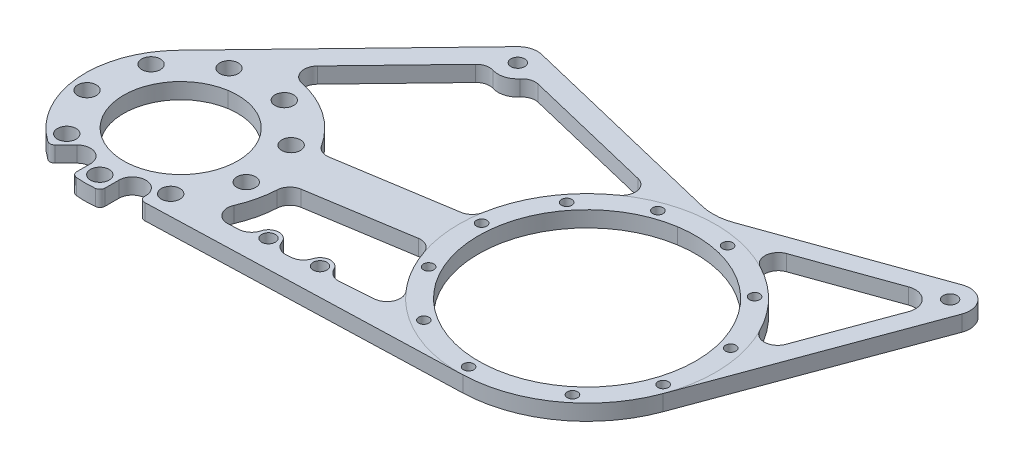
SolidWorks part; units mm, degrees
material "6061-T6 (SS)"
ref_plane "X-Y Datum" through (0, 0, 0) normal (0, 0, 1) x (1, 0, 0)
ref_plane "X-Z Datum" through (0, 0, 0) normal (0, 1, 0) x (1, 0, 0)
ref_plane "Y-Z Datum" through (0, 0, 0) normal (1, 0, 0) x (0, 0, -1)
sketch "Sketch3" plane through (0, 0, 0) normal (0, 1, 0) x (-1, 0, 0)
  line L0 (-549.8243, 18.1523) -> (-469.5602, 101.4499)
  line L1 (-673.8096, 168.3573) -> (-525.126, 173.1137)
  line L2 (-768.7537, 22.6435) -> (-729.9149, 127.9078)
  line L3 (-756.6081, 10.3783) -> (-668.3871, 41.9507)
  line L4 (-668.3871, 41.9507) -> (-558.9202, 15.5028)
  line L5 (-671.83, 106.4765) -> (-502.666, 133.35) construction
  line L8 (-479.4661, 170.6667) -> (-484.731, 165.4018)
  line L9 (-495.8272, 169.998) -> (-495.8272, 176.5707)
  line L10 (-509.5048, 176.5707) -> (-509.5048, 169.998)
  line L11 (-522.5048, 169.998) -> (-522.5048, 170.575)
  circle A1 centre (-759.8176, 19.3463) radius 9.525 construction
  circle A2 centre (-671.83, 106.4765) radius 61.9125 construction
  arc A4 (-671.83, 166.1265) -> (-671.83, 161.1265) centre (-671.83, 163.6265) ccw
  arc A5 (-671.83, 161.1265) -> (-671.83, 166.1265) centre (-671.83, 163.6265) ccw
  circle A8 centre (-556.6832, 24.7614) radius 9.525 construction
  circle A9 centre (-556.6832, 24.7614) radius 3.3
  arc A10 (-768.7537, 22.6435) -> (-756.6081, 10.3783) centre (-759.8176, 19.3463) ccw
  arc A11 (-558.9202, 15.5028) -> (-549.8243, 18.1523) centre (-556.6832, 24.7614) ccw
  arc A12 (-729.9149, 127.9078) -> (-673.8096, 168.3573) centre (-671.83, 106.4765) cw
  arc A13 (-525.126, 173.1137) -> (-522.5048, 170.575) centre (-525.0448, 170.575) cw
  arc A14 (-476.2083, 170.9479) -> (-469.5602, 101.4499) centre (-502.666, 133.35) cw
  arc A16 (-526.3535, 172.7519) -> (-476.2083, 170.9479) centre (-502.666, 133.35) ccw construction
  arc A17 (-476.2083, 170.9479) -> (-479.4661, 170.6667) centre (-477.6701, 168.8707) ccw
  arc A18 (-495.8272, 169.998) -> (-484.731, 165.4018) centre (-489.3272, 169.998) ccw
  arc A19 (-495.8272, 176.5707) -> (-498.1158, 179.0983) centre (-498.3672, 176.5707) ccw
  arc A20 (-498.1158, 179.0983) -> (-507.2162, 179.0983) centre (-502.666, 133.35) ccw
  arc A21 (-507.2162, 179.0983) -> (-509.5048, 176.5707) centre (-506.9648, 176.5707) ccw
  arc A22 (-522.5048, 169.998) -> (-509.5048, 169.998) centre (-516.0048, 169.998) ccw
  arc A23 (-522.5048, 170.575) -> (-526.3535, 172.7519) centre (-525.0448, 170.575) ccw construction
  arc A24 (-761.9822, 21.8372) -> (-757.653, 16.8554) centre (-759.8176, 19.3463) ccw
  arc A25 (-757.653, 16.8554) -> (-761.9822, 21.8372) centre (-759.8176, 19.3463) ccw
  arc A27 (-752.0152, 13.883) -> (-766.0654, 26.536) centre (-759.8176, 19.3463) ccw construction
  arc A29 (-548.0506, 28.7869) -> (-566.0335, 22.9455) centre (-556.6832, 24.7614) ccw construction
  arc A31 (-553.4437, 25.3906) -> (-559.9227, 24.1323) centre (-556.6832, 24.7614) ccw
  circle A33 centre (-502.666, 172.35) radius 4.5
  circle A36 centre (-502.666, 133.35) radius 27.4955
  circle A37 centre (-671.83, 106.4765) radius 52.3875
  dimension "D1" = 54.991
  dimension "D2" = 9
  dimension "D3" = 104.775
  dimension "D4" = 123.825
  dimension "D5" = 2.5
  dimension "D6" = 45.974
  dimension "D7" = 2.54
  dimension "D8" = 6.5
  dimension "D9" = 3.3
  dimension "D10" = 9.525
  dimension "D11" = 476.2083
  dimension "D12" = 477.6701
  dimension "D13" = 479.4661
  dimension "D14" = 484.731
  dimension "D15" = 13.883
  dimension "D16" = 22.9455
  dimension "D17" = 133.35
  dimension "D25" = 548.0506
  dimension "D26" = 553.4437
  dimension "D27" = 556.6832
  dimension "D28" = 559.9227
  dimension "D29" = 566.0335
  dimension "D30" = 671.83
  dimension "D31" = 752.0152
  dimension "D32" = 757.653
  dimension "D33" = 759.8176
  dimension "D34" = 761.9822
  dimension "D35" = 766.0654
  dimension "D36" = 106.4765
  dimension "D38" = 163.6265
  dimension "D45" = 172.35
extrude "Boss-Extrude2" add sketch "Sketch3" along normal blind 7.62 contours A22 L11 A13 L1 A12 L2 A10 L3 L4 A11 L0 A14 A17 L8 A18 L9 A19 A20 A21 L10 A37 A36 A33 A25 A24 A9 A5 A4 region at (600.4617, 0, 92.9965)
pattern_circular "CirPattern3" count 11 every 32 about axis through (671.83, 7.62, 106.4765) along (0, -1, 0) of face at (671.83, 7.62, 166.1265)
ref_point "Point1"
ref_point "Point2"
ref_plane "Plane1" through (671.83, 0, 106.4765) normal (-0.9876, 0, 0.1569) x (0.1569, 0, 0.9876)
ref_plane "Plane2" through (502.666, 0, 133.35) normal (-0.9876, 0, 0.1569) x (0.1569, 0, 0.9876)
split line "Split Line1"
split line "Split Line2"
sketch "Sketch4" plane through (0, 7.62, 0) normal (0, 1, 0) x (1, 0, 0)
  arc A0 (673.8096, -168.3573) -> (729.9149, -127.9078) centre (671.83, -106.4765) ccw construction
  arc A1 (673.8096, -168.3573) -> (729.9149, -127.9078) centre (671.83, -106.4765) ccw
  circle A2 centre (671.83, -106.4765) radius 61.9125
split line "Split Line3"
pattern_circular "CirPattern4" count 9 over 360 about axis through (502.666, 7.62, 133.35) along (0, -1, 0) of face at (502.666, 7.62, 176.85)
sketch "Sketch5" plane through (0, 7.62, 0) normal (0, 1, 0) x (1, 0, 0)
  line L0 (759.8176, -19.3463) -> (715.8226, -62.9126) construction
  line L1 (754.8899, -34.5364) -> (732.6394, -94.8414)
  line L2 (744.58, -24.1251) -> (684.06, -45.7839)
  line L3 (673.8096, -168.3573) -> (525.126, -173.1137) construction
  line L4 (756.6081, -10.3783) -> (668.3871, -41.9507) construction
  line L5 (756.6081, -10.3783) -> (668.3871, -41.9507) construction
  line L6 (768.7537, -22.6435) -> (729.9149, -127.9078) construction
  line L7 (768.7537, -22.6435) -> (729.9149, -127.9078) construction
  line L15 (556.6832, -24.7614) -> (556.6832, 0)
  line L16 (556.6832, 0) -> (624.6859, 0)
  line L17 (569.8883, 0) -> (569.8883, -158.2149) construction
  line L18 (593.9802, 0) -> (593.9802, -157.4442) construction
  line L19 (673.8096, -168.3573) -> (525.126, -173.1137) construction
  line L22 (593.9802, -157.4442) -> (569.8883, -158.2149) construction
  circle A0 centre (556.6832, -24.7614) radius 9.525 construction
  circle A1 centre (556.6832, -24.7614) radius 3.3 construction
  arc A2 (757.653, -16.8554) -> (761.9822, -21.8372) centre (759.8176, -19.3463) ccw construction
  arc A3 (761.9822, -21.8372) -> (757.653, -16.8554) centre (759.8176, -19.3463) ccw construction
  circle A4 centre (556.6832, -24.7614) radius 9.525 construction
  circle A5 centre (556.6832, -24.7614) radius 3.3 construction
  arc A6 (757.653, -16.8554) -> (761.9822, -21.8372) centre (759.8176, -19.3463) ccw construction
  arc A7 (761.9822, -21.8372) -> (757.653, -16.8554) centre (759.8176, -19.3463) ccw construction
  circle A8 centre (759.8176, -19.3463) radius 9.525 construction
  circle A9 centre (759.8176, -19.3463) radius 9.525 construction
  circle A10 centre (747.3044, -31.7376) radius 8.0853 construction
  circle A11 centre (569.8883, -158.2149) radius 3.3
  arc A13 (729.9149, -127.9078) -> (673.8096, -168.3573) centre (671.83, -106.4765) ccw construction
  arc A15 (754.8899, -34.5364) -> (744.58, -24.1251) centre (747.3044, -31.7376) ccw
  circle A31 centre (593.9802, -157.4442) radius 3.3
  circle A32 centre (593.9802, -157.4442) radius 5.08 construction
  circle A33 centre (569.8883, -158.2149) radius 5.08 construction
  arc A34 (732.6394, -94.8414) -> (684.06, -45.7839) centre (671.83, -106.4765) ccw
  dimension "D14" = 6.6
  dimension "D16" = 10.16
  dimension "D1" = 8.89
  dimension "D2" = 8.89
  dimension "D5" = 24.7614
  dimension "D7" = 13.2051
  dimension "D9" = 10.16
  dimension "D11" = 24.092
extrude "Cut-Extrude1" cut sketch "Sketch5" against normal blind 7.62 contours A34 L1 A15 L2 | A31 | A11 region at (728.4769, 7.62, 50.3816) region at (569.8883, 7.62, 158.2149) region at (593.9802, 7.62, 157.4442)
sketch "Sketch7" plane through (0, 7.62, 0) normal (0, 1, 0) x (1, 0, 0)
  line L0 (611.6874, -121.1745) -> (551.7434, -130.6972)
  line L1 (610.2378, -100.187) -> (546.1139, -110.3738)
  line L2 (610.6843, -116.1901) -> (551.2063, -125.6388) construction
  line L3 (671.83, -106.4765) -> (502.666, -133.35) construction
  line L6 (650.9516, -48.1905) -> (565.7721, -27.6106)
  line L7 (550.546, -32.0457) -> (500.232, -84.2613)
  line L9 (549.8243, -18.1523) -> (469.5602, -101.4499) construction
  line L10 (668.3871, -41.9507) -> (558.9202, -15.5028) construction
  line L11 (549.8243, -18.1523) -> (469.5602, -101.4499) construction
  line L12 (598.5841, -159.5915) -> (635.8764, -156.8798)
  line L13 (589.7354, -160.2349) -> (573.854, -161.3897)
  line L14 (565.9226, -161.3897) -> (542.3119, -162.3987)
  arc A2 (650.9516, -48.1905) -> (610.2378, -100.187) centre (671.83, -106.4765) ccw
  circle A3 centre (593.9802, -157.4442) radius 3.3 construction
  arc A4 (527.9894, -175.4731) -> (474.3811, -173.5444) centre (502.666, -133.35) ccw
  arc A5 (527.9894, -175.4731) -> (474.3811, -173.5444) centre (502.666, -133.35) ccw construction
  circle A6 centre (569.8883, -158.2149) radius 3.3 construction
  circle A7 centre (593.9802, -157.4442) radius 3.3
  circle A8 centre (569.8883, -158.2149) radius 3.3
  arc A9 (635.8764, -156.8798) -> (611.6874, -121.1745) centre (671.83, -106.4765) cw
  circle A10 centre (556.6832, -24.7614) radius 9.525 construction
  circle A11 centre (556.6832, -24.7614) radius 9.525 construction
  arc A12 (565.7721, -27.6106) -> (550.546, -32.0457) centre (556.6832, -24.7614) cw
  arc A13 (551.7434, -130.6972) -> (542.3119, -162.3987) centre (502.666, -133.35) cw
  arc A14 (546.1139, -110.3738) -> (500.232, -84.2613) centre (502.666, -133.35) ccw
  circle A15 centre (593.9802, -157.4442) radius 5.08 construction
  circle A16 centre (593.9802, -157.4442) radius 5.08 construction
  circle A17 centre (569.8883, -158.2149) radius 5.08 construction
  circle A18 centre (569.8883, -158.2149) radius 5.08 construction
  arc A19 (598.5841, -159.5915) -> (589.7354, -160.2349) centre (593.9802, -157.4442) ccw
  arc A20 (573.854, -161.3897) -> (565.9226, -161.3897) centre (569.8883, -158.2149) ccw
  arc A21 (684.06, -45.7839) -> (673.8096, -168.3573) centre (671.83, -106.4765) ccw construction
  dimension "D2" = 10.16
  dimension "D3" = 10.16
  dimension "D4" = 20.955
  dimension "D5" = 15.875
  dimension "D1" = 3.175
extrude "Cut-Extrude2" cut sketch "Sketch7" against normal blind 7.62 contours L1 A14 L7 A12 L6 A2 | A20 L14 A13 L0 A9 L12 A19 L13
fillet "Fillet1" radius 6.5024 16 edges at (611.6874, 3.81, 121.1745) (551.7434, 3.81, 130.6972) (542.3119, 3.81, 162.3987) (635.8764, 3.81, 156.8798) (565.9226, 3.81, 161.3897) (573.854, 3.81, 161.3897) (589.7354, 3.81, 160.2349) (598.5841, 3.81, 159.5915) (650.9516, 3.81, 48.1905) (565.7721, 3.81, 27.6106) (550.546, 3.81, 32.0457) (500.232, 3.81, 84.2613) (546.1139, 3.81, 110.3738) (610.2378, 3.81, 100.187) (732.6394, 3.81, 94.8414) (684.06, 3.81, 45.7839)
fillet "Fillet2" radius 25.4 1 edges at (668.3871, 3.81, 41.9507)
